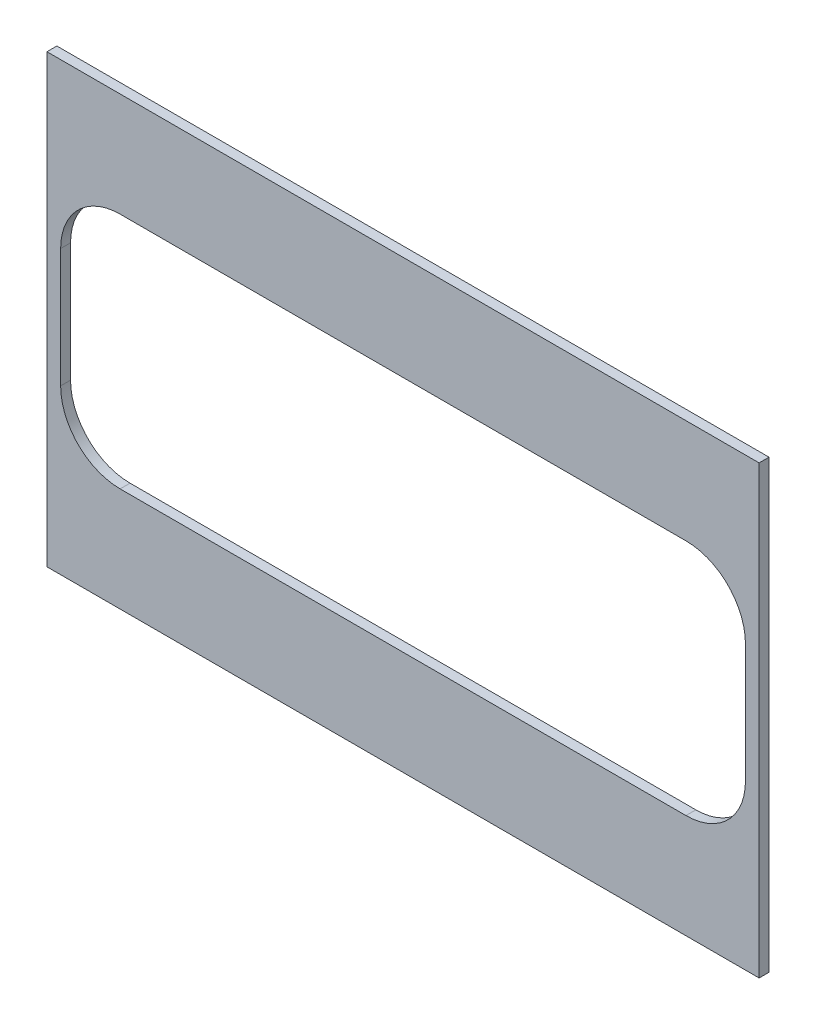
SolidWorks part; units mm, degrees
material "MDF"
ref_plane "Front Plane" through (0, 0, 0) normal (0, 0, 1) x (1, 0, 0)
ref_plane "Top Plane" through (0, 0, 0) normal (0, 1, 0) x (1, 0, 0)
ref_plane "Right Plane" through (0, 0, 0) normal (1, 0, 0) x (0, 0, -1)
sketch "Sketch1" plane through (0, 0, 0) normal (0, 0, 1) x (1, 0, 0)
  line L1 (-228.0888, 0) -> (228.0888, 0)
  line L2 (-228.0888, 0) -> (-228.0888, -285.75)
  line L3 (-228.0888, -285.75) -> (228.0888, -285.75)
  line L4 (228.0888, 0) -> (228.0888, -285.75)
  line L5 (58.5462, -285.75) -> (228.0888, -285.75) construction
  line L7 (228.0888, -3.175) -> (228.0888, -412.75) construction
  line L8 (228.0888, -412.75) -> (228.0888, -285.75) construction
  line L9 (-228.0888, -3.175) -> (-228.0888, -412.75) construction
  line L11 (-209.0388, 0) -> (-228.0888, 0) construction
extrude "Boss-Extrude1" add sketch "Sketch1" along normal blind 6.35
sketch "Sketch2" plane through (0, 0, 6.35) normal (0, 0, 1) x (1, 0, 0)
  line L0 (0, -285.75) -> (0, 0) construction
  line L1 (-228.0888, -285.75) -> (228.0888, -285.75) construction
  line L2 (228.0888, -285.75) -> (228.0888, 0) construction
  line L3 (-219.3258, -219.075) -> (219.3258, -219.075)
  line L4 (-219.3258, -219.075) -> (-219.3258, -66.675)
  line L5 (-219.3258, -66.675) -> (219.3258, -66.675)
  line L6 (219.3258, -219.075) -> (219.3258, -66.675)
  line L7 (-219.3258, -219.075) -> (219.3258, -66.675) construction
  line L8 (-219.3258, -66.675) -> (219.3258, -219.075) construction
  point P4 (0, -142.875)
  dimension "D1" = 8.763
  dimension "D2" = 152.4
extrude "Cut-Extrude1" cut sketch "Sketch2" against normal up to next
fillet "Fillet1" radius 38.1 4 edges at (219.3258, -66.675, 3.175) (219.3258, -219.075, 3.175) (-219.3258, -219.075, 3.175) (-219.3258, -66.675, 3.175)
